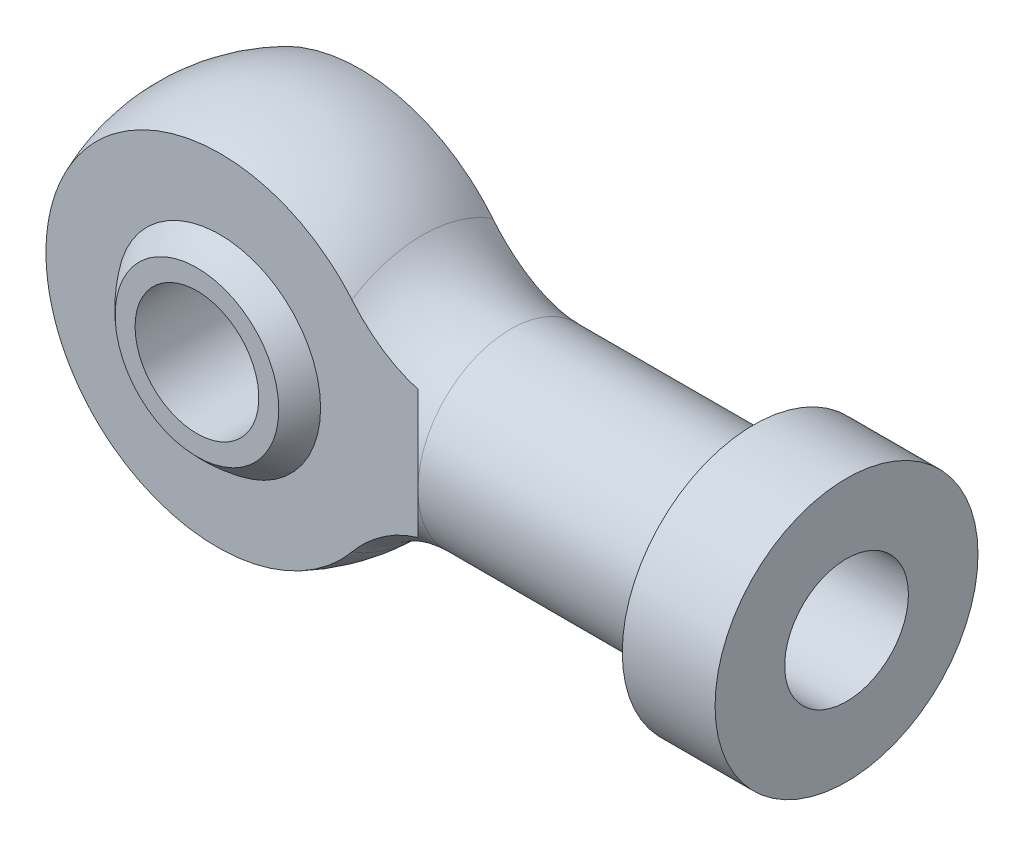
SolidWorks part; units mm, degrees
ref_plane "前视基准面" through (0, 0, 0) normal (0, 0, 1) x (1, 0, 0)
ref_plane "上视基准面" through (0, 0, 0) normal (0, 1, 0) x (1, 0, 0)
ref_plane "右视基准面" through (0, 0, 0) normal (1, 0, 0) x (0, 0, -1)
sketch "草图1" plane through (0, 0, 0) normal (0, 0, 1) x (1, 0, 0)
  line L0 (0, 0) -> (36, 0) construction
  line L1 (0, 0) -> (-12, 0) construction
  line L2 (36, -4) -> (36, 4)
  line L3 (36, 0) -> (-12, 0)
  line L5 (14.2829, 6) -> (30, 6)
  line L6 (30, -8.5) -> (30, 8.5)
  line L7 (30, 8.5) -> (36, 8.5)
  line L8 (36, 8.5) -> (36, 0)
  line L9 (14.2829, -6) -> (30, -6)
  line L10 (30, -8.5) -> (36, -8.5)
  line L11 (36, -8.5) -> (36, 0)
  line L12 (14.2829, 6) -> (14.2829, -6)
  circle A0 centre (0, 0) radius 12
  circle A1 centre (0, 0) radius 4
  arc A2 (8.5697, 8.4) -> (14.2829, 6) centre (14.2829, 14) ccw
  arc A3 (14.2829, -6) -> (8.5697, -8.4) centre (14.2829, -14) ccw
revolve "旋转3" add sketch "草图1" angle 360 about L3 region at (33, 4.25, 0) region at (22.1414, 3, 0) region at (12.646, 3.6078, 0) region at (0, 5.5174, 0)
ref_plane "基准面2" through (0, 0, 0) normal (0, 1, 0) x (1, 0, 0)
sketch "草图2" plane through (0, 0, 0) normal (0, 1, 0) x (1, 0, 0)
  line L0 (14.2829, 6) -> (14.2829, -6)
  line L1 (14.2829, 6) -> (5.6303, 10.5971)
  line L2 (14.2829, -6) -> (5.6303, -10.5971)
  line L16 (12.7964, 4.5136) -> (14.2829, 6)
  line L17 (12.7964, -4.5136) -> (14.2829, -6)
  line L18 (-5.2915, 6) -> (5.2915, 6)
  line L19 (-5.2915, -6) -> (5.2915, -6)
  line L20 (-11.028, 4.731) -> (12.7964, 4.5136)
  line L21 (12.7964, -4.5136) -> (-11.028, -4.731)
  arc A0 (-11.028, 4.731) -> (-11.028, -4.731) centre (0, 0) ccw
  arc A1 (-5.2915, 6) -> (-6.4865, 4.6825) centre (0, 0) ccw
  arc A2 (-6.4865, -4.6825) -> (-5.2915, -6) centre (0, 0) ccw
  arc A3 (6.5659, -4.5704) -> (6.5708, -4.5633) centre (0, 0) ccw
  arc A4 (6.5708, 4.5633) -> (6.5659, 4.5704) centre (0, 0) ccw
  circle A5 centre (0, 0) radius 12
  dimension "D2" = 24
  dimension "D1" = 12
extrude "切除-拉伸1" cut sketch "草图2" against normal mid plane 25 contours L20 A5 A1 L18 A4 | A5 L20 L16 L1 | A5 L21 A3 L19 A2 | A5 L2 L17 L21 region at (11.2473, 0, -6.5524) region at (11.2473, 0, 6.5524) region at (0.07, 0, -7.6724) region at (0.07, 0, 7.6724)
sketch "草图3" plane through (0, 0, 0) normal (0, 1, 0) x (1, 0, 0)
  line L0 (6.5708, 4.5633) -> (6.5708, -4.5633)
  line L22 (-5.2915, 6) -> (5.2915, 6)
  line L23 (-5.2915, -6) -> (5.2915, -6)
  line L24 (-6.4865, 4.6825) -> (6.5708, 4.5633)
  line L25 (6.5708, -4.5633) -> (-6.4865, -4.6825)
  line L26 (0, 6) -> (0, -6)
  arc A5 (-6.4865, -4.6825) -> (-5.2915, -6) centre (0, 0) ccw
  arc A6 (5.2915, -6) -> (6.5708, -4.5633) centre (0, 0) ccw
  arc A7 (6.5708, 4.5633) -> (5.2915, 6) centre (0, 0) ccw
  arc A8 (-5.2915, 6) -> (-6.4865, 4.6825) centre (0, 0) ccw
revolve "旋转6" add sketch "草图3" angle 360 about L26 region at (3.2783, 0, 0) region at (3.0219, 0, -5.272) region at (3.0219, 0, 5.272)
sketch "草图4" plane through (0, 0, -6) normal (0, 0, -1) x (-1, 0, 0)
  circle A0 centre (0, 0) radius 4
  dimension "D1" = 8
extrude "切除-拉伸2" cut sketch "草图4" against normal blind 21
sketch "草图6" plane through (36, 0, 0) normal (1, 0, 0) x (0, 0, -1)
  circle A0 centre (0, 0) radius 4
  dimension "D1" = 8
extrude "切除-拉伸3" cut sketch "草图6" against normal blind 21
